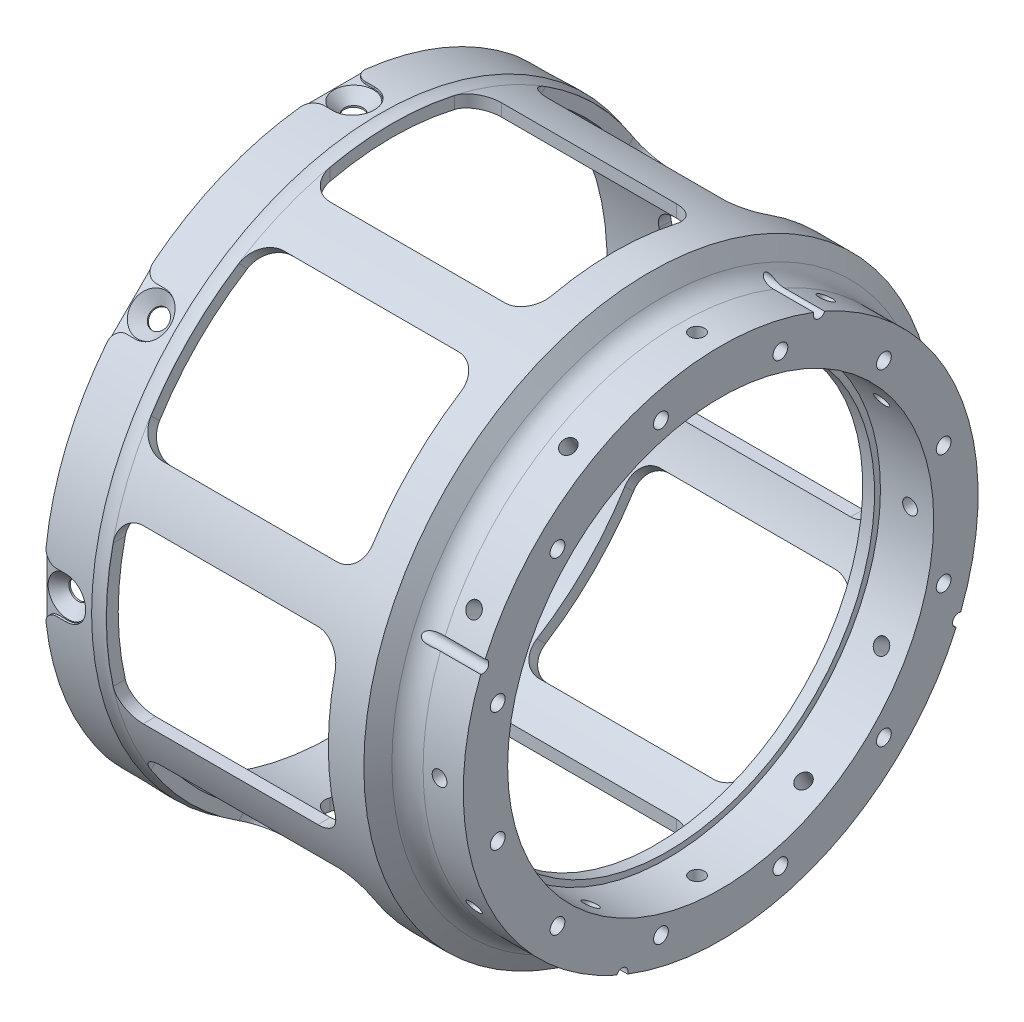
SolidWorks part; units mm, degrees
material "6061 Alloy"
ref_plane "Front Plane" through (0, 0, 0) normal (0, 0, 1) x (1, 0, 0)
ref_plane "Top Plane" through (0, 0, 0) normal (0, 1, 0) x (1, 0, 0)
ref_plane "Right Plane" through (0, 0, 0) normal (1, 0, 0) x (0, 0, -1)
sketch "Sketch1" plane through (0, 0, 0) normal (0, 0, 1) x (1, 0, 0)
  line L0 (0, 0) -> (67.3485, 0) construction
  line L1 (0, 0) -> (0, 46.3) construction
  line L2 (0, 46.3) -> (50, 46.3)
  line L3 (50, 46.3) -> (50, 44)
  line L4 (50, 44) -> (53.5, 44)
  line L5 (53.5, 44) -> (53.5, 42)
  line L6 (53.5, 42) -> (54.5, 42) construction
  line L7 (54.5, 42) -> (54.5, 35) construction
  line L8 (54.5, 35) -> (56.5, 35)
  line L9 (56.5, 35) -> (56.5, 36)
  line L10 (56.5, 36) -> (65.5, 36)
  line L11 (65.5, 36) -> (65.5, 43.5)
  line L12 (65.5, 43.5) -> (56.5, 43.5)
  line L14 (53.5, 48.3) -> (8, 48.3)
  line L15 (8, 48.3) -> (8, 48.8)
  line L16 (8, 48.8) -> (0, 48.8)
  line L17 (0, 48.8) -> (0, 46.3)
  line L18 (56.5, 43.5) -> (53.5, 48.3)
  line L19 (53.5, 42) -> (54.5, 35)
  point P19 (51.75, 44)
  point P20 (54, 42)
  dimension "D1" = 46.3
  dimension "D2" = 50
  dimension "D3" = 3.5
  dimension "D4" = 1
  dimension "D5" = 2
  dimension "D6" = 9
  dimension "D7" = 9
  dimension "D8" = 8
  dimension "D9" = 2.5
  dimension "D10" = 2
  dimension "D11" = 44
  dimension "D12" = 42
  dimension "D13" = 36
  dimension "D14" = 1
  dimension "D15" = 7.5
revolve "Revolve1" add sketch "Sketch1" angle 360 about L0
sketch "Sketch2" plane through (0, 0, 0) normal (0, 0, 1) x (1, 0, 0)
  line L0 (8, 0) -> (53.5, 0) construction
  line L1 (53.5, -48.3) -> (53.5, 48.3) construction
  line L2 (8, -48.8) -> (8, 48.8) construction
  line L4 (30.75, 48.3) -> (30.75, -48.3) construction
  line L5 (53.5, 48.3) -> (8, 48.3) construction
  line L6 (8, -48.3) -> (53.5, -48.3) construction
  line L8 (10, 14.5) -> (47.5, 14.5)
  line L9 (10, 14.5) -> (10, -14.5)
  line L10 (10, -14.5) -> (47.5, -14.5)
  line L11 (47.5, 14.5) -> (47.5, -14.5)
  point P13 (30.75, 0)
  point P20 (47.5, 0)
  dimension "D1" = 6
  dimension "D2" = 29
  dimension "D3" = 2
extrude "Cut-Extrude1" cut sketch "Sketch2" against normal through all
fillet "Fillet1" radius 4 4 edges at (47.5, -14.5, -45.0215) (10, -14.5, -45.0215) (10, 14.5, -45.0215) (47.5, 14.5, -45.0215)
pattern_circular "CirPattern1" count 8 over 360 about axis through (8, 0, 0) along (-1, 0, 0) of "Fillet1", "Cut-Extrude1"
sketch "Sketch3" plane through (0, 0, 0) normal (0, 0, 1) x (1, 0, 0)
  line L0 (0, 0) -> (3.5, 0) construction
  circle A0 centre (3.5, 0) radius 1.5
  dimension "D1" = 3
  dimension "D2" = 3.5
extrude "Cut-Extrude2" cut sketch "Sketch3" against normal through all
pattern_circular "CirPattern2" count 8 over 360 about axis through (0, 0, 0) along (-1, 0, 0) of "Cut-Extrude2"
ref_plane "Plane1" through (0, 0, 48.8) normal (0, 0, 1) x (1, 0, 0)
sketch "Sketch7" plane through (0, 0, 48.8) normal (0, 0, 1) x (1, 0, 0)
  line L0 (3.5, 3.5) -> (-4.5, 3.5)
  line L1 (-4.5, 3.5) -> (-4.5, -3.5)
  line L2 (-4.5, -3.5) -> (3.5, -3.5)
  arc A0 (3.5, -3.5) -> (3.5, 3.5) centre (3.5, 0) ccw
  dimension "D2" = 8
extrude "Cut-Extrude3" cut sketch "Sketch7" against normal blind 0.5
fillet "Fillet3" radius 2 2 edges at (0, -3.5, 48.4872) (0, 3.5, 48.4872)
pattern_circular "CirPattern3" count 8 over 360 about axis through (0, 0, 0) along (-1, 0, 0) of "Cut-Extrude3", "Fillet3"
hole_wizard "CSK for M3 Flat Head Machine Screw2" positions "Sketch10" profile "Sketch11" countersink size "M3" standard "ANSI Metric" end condition through all
sketch "Sketch10" plane through (0, 0, 48.3) normal (0, 0, 1) x (1, 0, 0)
  point P0 (3.5, 0)
sketch "Sketch11" plane through (3.5, 0, 48.3) normal (1, 0, 0) x (0, -1, 0)
  line L0 (0, 0) -> (0, 117.3136)
  line L1 (0, 117.3136) -> (1.6, 117.3136)
  line L2 (1.6, 117.3136) -> (1.6, 1.75)
  line L3 (1.6, 1.75) -> (3.35, 0)
  line L5 (3.35, 0) -> (0, 0)
  line L6 (-1.6, 1.75) -> (-3.35, 0) construction
  line L11 (0, -6.35) -> (0, 107.95) construction
  dimension "Thru Hole Dia." = 3.2
  dimension "Thru Hole Depth" = 117.3136
  dimension "Near C'Sink Dia." = 6.7
  dimension "Near C'Sink Angle" = 90
pattern_circular "CirPattern4" count 8 over 360 about axis through (0, 0, 0) along (-1, 0, 0) of "CSK for M3 Flat Head Machine Screw2"
sketch "Sketch12" plane through (0, 0, 0) normal (0, 0, 1) x (1, 0, 0)
  line L0 (61.5, 0) -> (65.5, 0) construction
  line L1 (65.5, -43.5) -> (65.5, 43.5) construction
  circle A0 centre (61.5, 0) radius 1.25
  dimension "D1" = 2.5
  dimension "D2" = 4
extrude "Cut-Extrude4" cut sketch "Sketch12" against normal through all
pattern_circular "CirPattern5" count 12 over 360 about axis through (65.5, 0, 0) along (-1, 0, 0) of "Cut-Extrude4"
sketch "Sketch13" plane through (65.5, 0, 0) normal (1, 0, 0) x (0, 0, -1)
  line L0 (0, 0) -> (0, 43.5) construction
  line L1 (0, 0) -> (-11.2586, 42.0178) construction
  circle A0 centre (0, 0) radius 43.5 construction
  circle A1 centre (0, 0) radius 43.5 construction
  circle A2 centre (-10.0939, 37.6711) radius 1.25
  circle A3 centre (0, 0) radius 36 construction
  dimension "D2" = 2.5
  dimension "D1" = 15
  dimension "D3" = 39
extrude "Cut-Extrude5" cut sketch "Sketch13" against normal through all
pattern_circular "CirPattern6" count 12 over 360 about axis through (65.5, 0, 0) along (-1, 0, 0) of "Cut-Extrude5"
sketch "Sketch14" plane through (53.5, 0, 0) normal (-1, 0, 0) x (0, 0, 1)
  line L0 (0, 0) -> (0, 46.3) construction
  line L1 (0, 0) -> (-17.3356, 41.8517) construction
  line L2 (0, 0) -> (-15.1215, 42.7017) construction
  line L3 (0, 0) -> (-19.5022, 40.8871) construction
  line L4 (-19.5022, 40.8871) -> (-18.9425, 39.7138)
  line L5 (-15.1215, 42.7017) -> (-14.6875, 41.4762)
  circle A0 centre (0, 0) radius 46.3 construction
  arc A1 (-19.5022, 40.8871) -> (-15.1215, 42.7017) centre (0, 0) cw
  arc A2 (-18.9425, 39.7138) -> (-14.6875, 41.4762) centre (0, 0) cw
  circle A3 centre (0, 0) radius 44 construction
  dimension "D1" = 22.5
  dimension "D2" = 3
  dimension "D3" = 1.3
extrude "Cut-Extrude6" cut sketch "Sketch14" along normal through all
fillet "Fillet4" radius 4 2 edges at (51.75, 39.7138, -18.9425) (51.75, 41.4762, -14.6875)
fillet "Fillet5" radius 4 2 edges at (51.75, 42.7017, -15.1215) (51.75, 40.8871, -19.5022)
pattern_circular "CirPattern7" count 4 over 360 about axis through (0, 0, 0) along (-1, 0, 0) of "Cut-Extrude6", "Fillet4", "Fillet5"
fillet "Fillet6" radius 4 1 edges at (8, 0, 48.3)
fillet "Fillet7" radius 4 1 edges at (56.5, 0, 43.5)
sketch "Sketch15" plane through (53.5, 0, 0) normal (-1, 0, 0) x (0, 0, 1)
  line L0 (0, 0) -> (-17.3356, 41.8517) construction
  line L1 (-17.3356, 41.8517) -> (-17.7182, 42.7756) construction
  arc A0 (-16.6031, 42.1477) -> (-18.0627, 41.5431) centre (0, 0) ccw construction
  circle A1 centre (-16.6467, 40.1888) radius 1
  circle A3 centre (0, 0) radius 46.3 construction
  dimension "D1" = 2
  dimension "D2" = 2.8
extrude "Cut-Extrude7" cut sketch "Sketch15" against normal through all
pattern_circular "CirPattern8" count 4 over 360 about axis through (65.5, 0, 0) along (-1, 0, 0) of "Cut-Extrude7"
